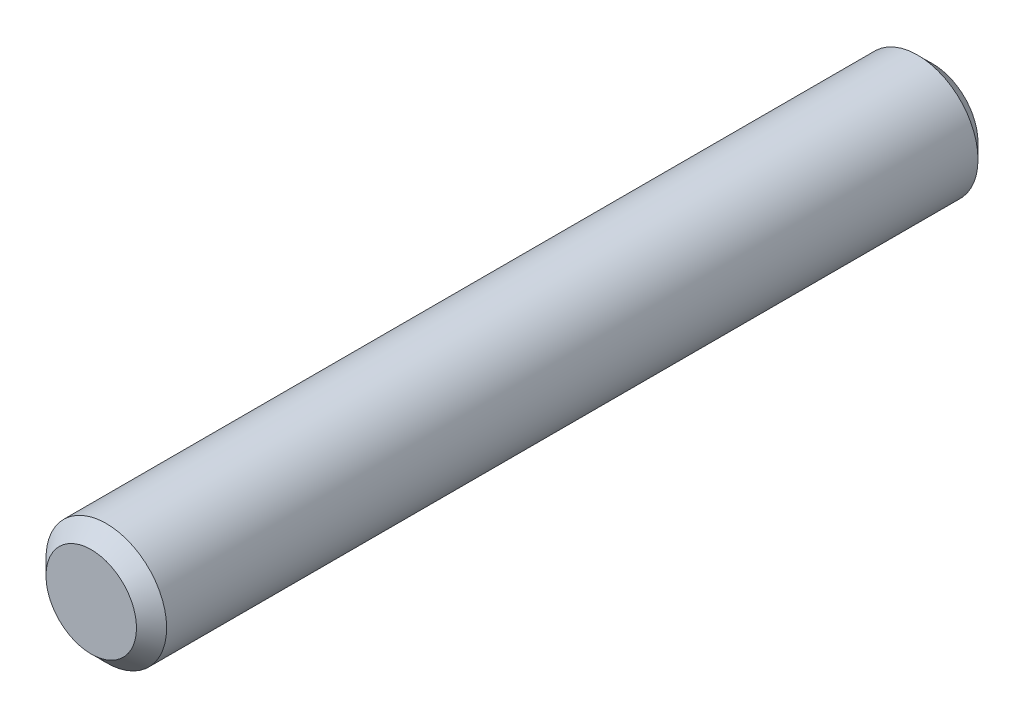
SolidWorks part; units mm, degrees
ref_plane "Front Plane" through (0, 0, 0) normal (0, 0, 1) x (1, 0, 0)
ref_plane "Top Plane" through (0, 0, 0) normal (0, 1, 0) x (1, 0, 0)
ref_plane "Right Plane" through (0, 0, 0) normal (1, 0, 0) x (0, 0, -1)
sketch "Sketch1" plane through (0, 0, 0) normal (0, 0, 1) x (1, 0, 0)
  circle A0 centre (0, 0) radius 5.08
  dimension "D1" = 10.16
extrude "Boss-Extrude1" add sketch "Sketch1" along normal blind 35.433 and the other way blind 35.433 contours A0
chamfer "Chamfer1" distance 1.27 angle 45 2 edges at (5.08, 0, 35.433) (5.08, 0, -35.433)
